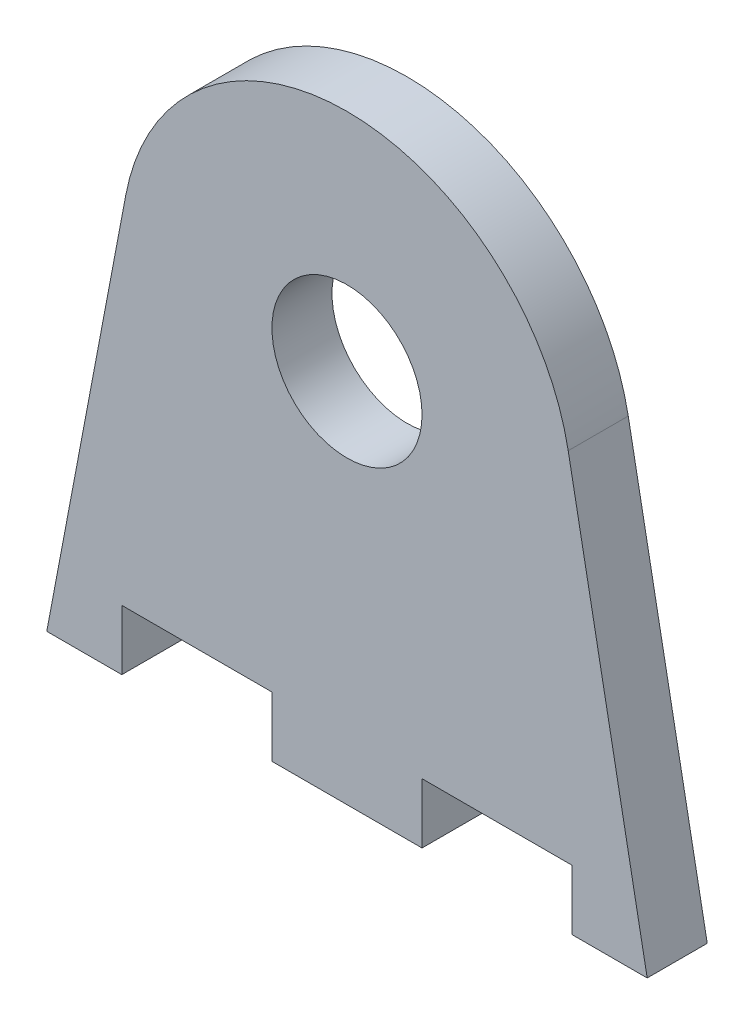
SolidWorks part; units mm, degrees
ref_plane "Front Plane" through (0, 0, 0) normal (0, 0, 1) x (1, 0, 0)
ref_plane "Top Plane" through (0, 0, 0) normal (0, 1, 0) x (1, 0, 0)
ref_plane "Right Plane" through (0, 0, 0) normal (1, 0, 0) x (0, 0, -1)
sketch "Sketch1" plane through (0, 0, 0) normal (0, 0, 1) x (1, 0, 0)
  line L2 (-20, -25) -> (-15, -25)
  line L3 (20, -25) -> (14.7381, 2.7905)
  line L4 (-20, -25) -> (-14.7381, 2.7905)
  line L5 (-5, -25) -> (5, -25)
  line L7 (-15, -25) -> (-15, -21)
  line L8 (-15, -21) -> (-5, -21)
  line L9 (-5, -25) -> (-5, -21)
  line L11 (5, -25) -> (5, -21)
  line L12 (5, -21) -> (15, -21)
  line L13 (15, -25) -> (15, -21)
  line L14 (15, -25) -> (20, -25)
  arc A3 (14.7381, 2.7905) -> (-14.7381, 2.7905) centre (0, 0) ccw
  circle A5 centre (0, 0) radius 5
  dimension "D1" = 20
  dimension "D2" = 20
  dimension "D4" = 15
  dimension "D3" = 10
  dimension "D5" = 25
  dimension "D6" = 4
  dimension "D7" = 4
  dimension "D8" = 10
  dimension "D9" = 10
  dimension "D10" = 5
  dimension "D11" = 10
extrude "Boss-Extrude2" add sketch "Sketch1" along normal blind 4
